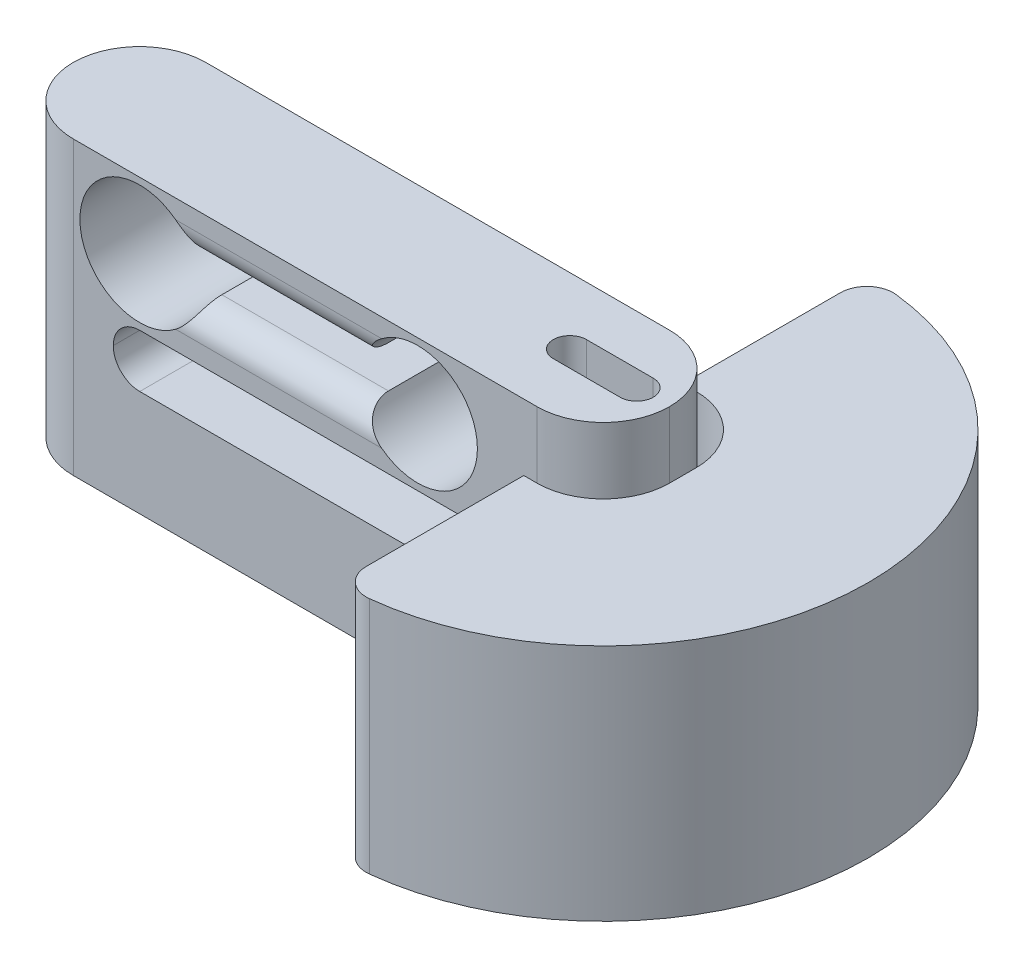
SolidWorks part; units mm, degrees
ref_plane "Front Plane" through (0, 0, 0) normal (0, 0, 1) x (1, 0, 0)
ref_plane "Top Plane" through (0, 0, 0) normal (0, 1, 0) x (1, 0, 0)
ref_plane "Right Plane" through (0, 0, 0) normal (1, 0, 0) x (0, 0, -1)
other "Center of Mass"
sketch "Sketch1" plane through (0, 0, 0) normal (0, 0, 1) x (1, 0, 0)
  line L0 (5, 0) -> (0, 0)
  line L1 (0, 0) -> (-5, 0)
  line L2 (-5, 0) -> (-35, 0)
  line L3 (5, 0) -> (5, -10)
  line L4 (5, -10) -> (-5, -10)
  line L5 (-5, -10) -> (-31.9826, -10)
  line L6 (-35, 0) -> (-40, 0)
  line L7 (-26.8791, -3.4207) -> (-11.5008, -3.4207)
  line L8 (-26.8791, -3.4207) -> (-26.8791, -6.5793)
  line L9 (-26.8791, -6.5793) -> (-11.5008, -6.5793)
  line L10 (-11.5008, -3.4207) -> (-11.5008, -6.5793)
  line L11 (-26.8791, -3.4207) -> (-11.5008, -6.5793) construction
  line L12 (-26.8791, -6.5793) -> (-11.5008, -3.4207) construction
  line L13 (-40, 0) -> (-40, -14)
  line L14 (-40, -14) -> (-31.9826, -14)
  line L15 (-31.9826, -14) -> (-31.9826, -10)
  circle A0 centre (-30, -5) radius 4.5
  circle A1 centre (-9, -5) radius 4.5
  point P12 (-19.1899, -5)
  point P17 (-40, 0)
  dimension "D5" = 5
  dimension "D6" = 5
  dimension "D7" = 9
  dimension "D8" = 9
  dimension "D1" = 5
  dimension "D2" = 5
  dimension "D3" = 30
  dimension "D4" = 10
  dimension "D9" = 4
  dimension "D10" = 40
  dimension "D11" = 14
extrude "Boss-Extrude1" add sketch "Sketch1" along normal blind 5 and the other way blind 5 contours L14 L15 L5 L4 L3 L0 L1 L2 L6 L13 A1 L9 A0 L7 region at (4.5287, -5, 0)
sketch "Sketch2" plane through (0, 0, 0) normal (0, 1, 0) x (1, 0, 0)
  line L0 (-2.521, 0) -> (2.521, 0) construction
  line L1 (-2.521, 1.25) -> (2.521, 1.25)
  line L2 (-2.521, -1.25) -> (2.521, -1.25)
  arc A0 (-2.521, 1.25) -> (-2.521, -1.25) centre (-2.521, 0) ccw
  arc A1 (2.521, -1.25) -> (2.521, 1.25) centre (2.521, 0) ccw
  point P2 (0, 0)
extrude "Cut-Extrude1" cut sketch "Sketch2" against normal blind 5
sketch "Sketch3" plane through (0, 0, 0) normal (0, 1, 0) x (1, 0, 0)
  line L0 (5, -5) -> (-40, -5) construction
  line L1 (-40, 5) -> (5.8816, 5)
  line L2 (-40, 5) -> (-40, -5)
  line L3 (-40, -5) -> (5.8816, -5)
  line L4 (5.8816, 5) -> (5.8816, -5)
  line L6 (-44.7352, 22.5342) -> (0, 22.5342)
  line L7 (-44.7352, 22.5342) -> (-44.7352, -27.8282)
  line L8 (-44.7352, -27.8282) -> (0, -27.8282)
  line L9 (0, 22.5342) -> (0, -27.8282)
  circle A0 centre (0, 0) radius 20
  point P14 (0, 0)
  dimension "D1" = 40
extrude "Boss-Extrude2" add sketch "Sketch3" against normal blind 8 from offset 14 contours L9 A0 L1 L4 L3 | L1 L9 L3 L4 | L1 A0 L3 L9 | A0 L1 L2 L3 region at (-29.894, 0, 0) region at (-9.8957, 0, 0) region at (9.0612, 0, 0) region at (2.9408, 0, 0) offset against normal yes
sketch "Sketch4" plane through (0, -14, 0) normal (0, 1, 0) x (1, 0, 0)
  line L0 (5, 5) -> (-40, 5) construction
  line L1 (0, 20) -> (46.8504, 20)
  line L2 (0, 20) -> (0, -35.9681)
  line L3 (0, -35.9681) -> (46.8504, -35.9681)
  line L4 (46.8504, 20) -> (46.8504, -35.9681)
  line L5 (6, 6) -> (-6.1468, 6)
  line L6 (6, 6) -> (6, -6)
  line L7 (6, -6) -> (-6.1468, -6)
  line L8 (-6.1468, 6) -> (-6.1468, -6)
  line L9 (5, -5) -> (-40, -5) construction
  line L10 (5, 5) -> (5, -5) construction
  circle A0 centre (0, 0) radius 20
  arc M8 (0, -20) -> (0, 20) centre (0, 0) ccw
  line M9 (0, 20) -> (0, 5)
  dimension "D4" = 40
  dimension "D1" = 1
  dimension "D2" = 1
  dimension "D3" = 1
extrude "Boss-Extrude3" add sketch "Sketch4" along normal blind 10 contours L6 L7 L2 L5 M8 M9 region at (9.1986, -14, 0)
fillet "Fillet2" radius 5 6 edges at (-40, -11, -5) (-40, -11, 5) (6, -9, 6) (6, -9, -6) (5, -5, 5) (5, -5, -5)
fillet "Fillet3" radius 2 8 edges at (-19.5, -3.4207, -5) (-19.5, -6.5793, -5) (-19.5, -6.5793, 5) (-19.5, -3.4207, 5) (-31.9826, -10, 0) (-31.9826, -14, 0) (0, -13, -20) (0, -13, 20)
sketch "Sketch5" plane through (0, -22, 0) normal (0, -1, 0) x (1, 0, 0)
  line L0 (-35, 0) -> (-12, 0) construction
  line L1 (-35, 3.25) -> (-12, 3.25)
  line L2 (-35, -3.25) -> (-12, -3.25)
  line L4 (-6.5, 1.5) -> (-3.5, 1.5)
  line L5 (-6.5, 1.5) -> (-6.5, -1.5)
  line L6 (-6.5, -1.5) -> (-3.5, -1.5)
  line L7 (-3.5, 1.5) -> (-3.5, -1.5)
  line L8 (-6.5, 1.5) -> (-3.5, -1.5) construction
  line L9 (-6.5, -1.5) -> (-3.5, 1.5) construction
  line L10 (3.5, 1.5) -> (6.5, 1.5)
  line L11 (3.5, 1.5) -> (3.5, -1.5)
  line L12 (3.5, -1.5) -> (6.5, -1.5)
  line L13 (6.5, 1.5) -> (6.5, -1.5)
  line L14 (3.5, 1.5) -> (6.5, -1.5) construction
  line L15 (3.5, -1.5) -> (6.5, 1.5) construction
  arc A0 (-35, 3.25) -> (-35, -3.25) centre (-35, 0) ccw
  arc A1 (-12, -3.25) -> (-12, 3.25) centre (-12, 0) ccw
  circle A3 centre (0, 0) radius 2
  point P3 (-23.5, 0)
  point P8 (-5, 0)
  point P13 (5, 0)
  dimension "D3" = 3
  dimension "D9" = 4
  dimension "D1" = 35
  dimension "D2" = 12
  dimension "D4" = 3
  dimension "D5" = 0
  dimension "D6" = 5
  dimension "D7" = 3
  dimension "D8" = 5
extrude "Cut-Extrude2" cut sketch "Sketch5" against normal blind 4
fillet "Fillet4" radius 1 7 edges at (-23.5, -18, 3.25) (-8.75, -18, 0) (-23.5, -18, -3.25) (-38.25, -18, 0) (0, -18, -5) (0, -18, 5) (0, -22, -2)
sketch "Sketch6" plane through (0, -22, 0) normal (0, -1, 0) x (1, 0, 0)
  circle A0 centre (-35, 0) radius 3.25
extrude "Cut-Extrude3" cut sketch "Sketch6" against normal blind 5
